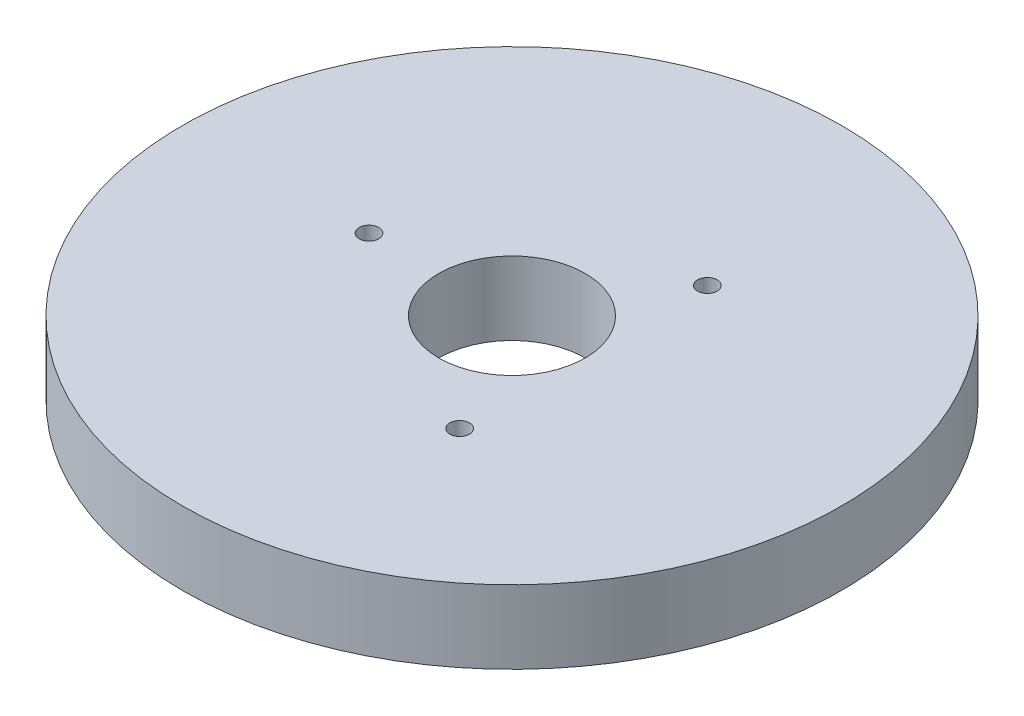
SolidWorks part; units mm, degrees
ref_plane "Front Plane" through (0, 0, 0) normal (0, 0, 1) x (1, 0, 0)
ref_plane "Top Plane" through (0, 0, 0) normal (0, 1, 0) x (1, 0, 0)
ref_plane "Right Plane" through (0, 0, 0) normal (1, 0, 0) x (0, 0, -1)
sketch "Sketch1" plane through (0, 0, 0) normal (0, 1, 0) x (1, 0, 0)
  circle A0 centre (0, 0) radius 90
  dimension "FLANGE_OD" = 180
extrude "Boss-Extrude1" add sketch "Sketch1" along normal blind 20
sketch "Sketch2" plane through (0, 0, 0) normal (0, 1, 0) x (1, 0, 0)
  circle A0 centre (0, 0) radius 20
  dimension "BORE_D" = 40
extrude "Cut-Extrude1" cut sketch "Sketch2" along normal through all
sketch "Sketch3" plane through (0, 20, 0) normal (0, 1, 0) x (1, 0, 0)
  circle A0 centre (0, 0) radius 39.058 construction
  circle A1 centre (-39.058, 0) radius 2.6758
  dimension "BOLT_D" = 5.3516
  dimension "BOLT_PCD" = 78.116
extrude "Cut-Extrude2" cut sketch "Sketch3" against normal blind 12.2493
pattern_circular "CirPattern1" count 3 over 360 about axis through (0, 0, 0) along (0, 1, 0) of "Cut-Extrude2"
